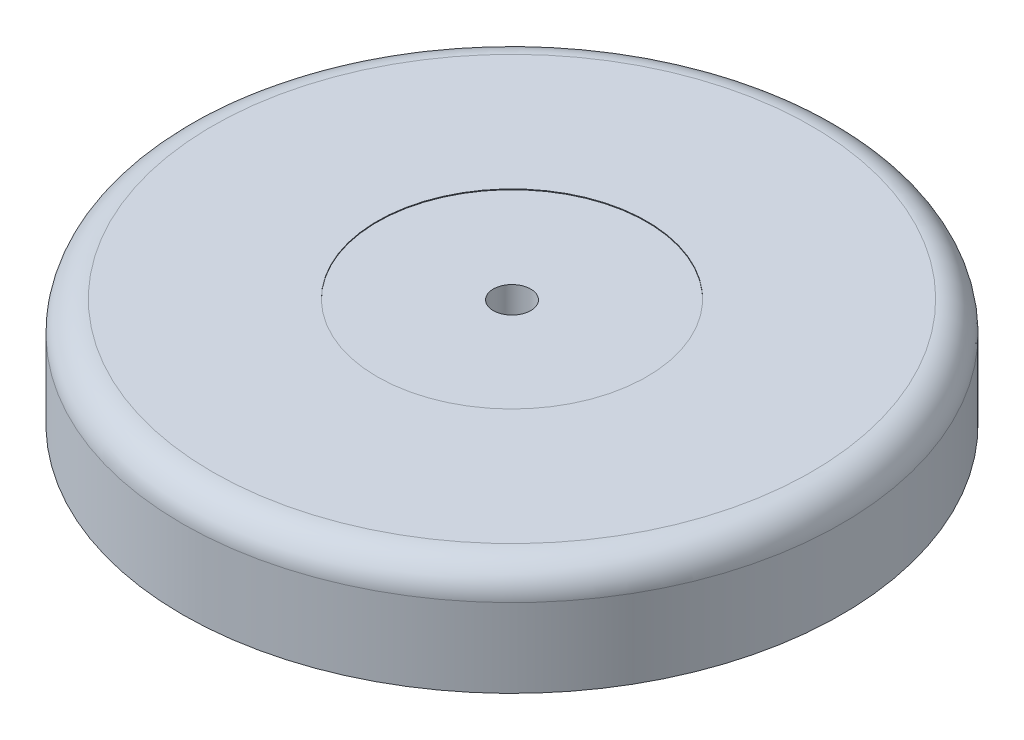
SolidWorks part; units mm, degrees
ref_plane "Front Plane" through (0, 0, 0) normal (0, 0, 1) x (1, 0, 0)
ref_plane "Top Plane" through (0, 0, 0) normal (0, 1, 0) x (1, 0, 0)
ref_plane "Right Plane" through (0, 0, 0) normal (1, 0, 0) x (0, 0, -1)
sketch "Sketch1" plane through (0, 0, 0) normal (0, 1, 0) x (1, 0, 0)
  circle A0 centre (0, 0) radius 44
extrude "Boss-Extrude1" add sketch "Sketch1" along normal blind 14.5
fillet "Fillet1" radius 4 1 edges at (0, 14.5, 44)
sketch "Sketch2" plane through (0, 14.5, 0) normal (0, 1, 0) x (1, 0, 0)
  circle A0 centre (0, 0) radius 18
extrude "Cut-Extrude1" cut sketch "Sketch2" against normal blind 0.1
sketch "Sketch3" plane through (0, 14.4, 0) normal (0, 1, 0) x (1, 0, 0)
  circle A0 centre (0, 0) radius 2.5
extrude "Cut-Extrude2" cut sketch "Sketch3" against normal through all
sketch "Sketch4" plane through (0, 0, 0) normal (0, -1, 0) x (1, 0, 0)
  circle A0 centre (0, 0) radius 7.5
  circle A1 centre (0, 0) radius 18
  circle A2 centre (0, 0) radius 18
  circle A3 centre (0, 0) radius 2.5 construction
  circle A4 centre (0, 0) radius 2.5
  circle M3 centre (0, 0) radius 2.5
  dimension "D1" = 0
extrude "Boss-Extrude2" add sketch "Sketch4" along normal blind 9.3 contours A0 M3 region at (-7.2879, 0, 0)
extrude "Cut-Extrude3" cut sketch "Sketch4<3>" against normal blind 0.1 contours A2 A0 region at (-17.4909, 0, 0)
sketch "Sketch4<3>" plane through (0, 0, 0) normal (0, -1, 0) x (1, 0, 0) same geometry as "Sketch4"
